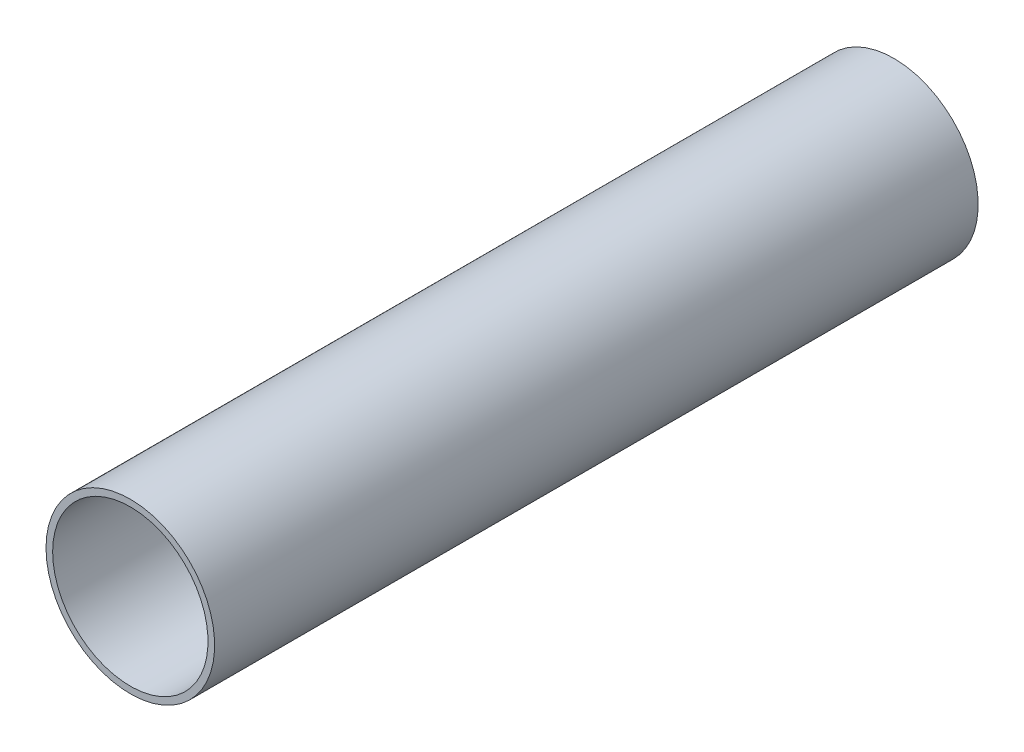
SolidWorks part; units mm, degrees
material "PVC Rigid"
ref_plane "Front Plane" through (0, 0, 0) normal (0, 0, 1) x (1, 0, 0)
ref_plane "Top Plane" through (0, 0, 0) normal (0, 1, 0) x (1, 0, 0)
ref_plane "Right Plane" through (0, 0, 0) normal (1, 0, 0) x (0, 0, -1)
sketch "Path" plane through (0, 0, 0) normal (1, 0, 0) x (0, 0, -1)
  line L0 (0, 0) -> (115, 0)
  dimension "Longitud" = 115
sweep "Sweep-Thin" add path "Path" circular profile diameter 1 parameters "Espesor"=1, "Diámetro"=25.4
